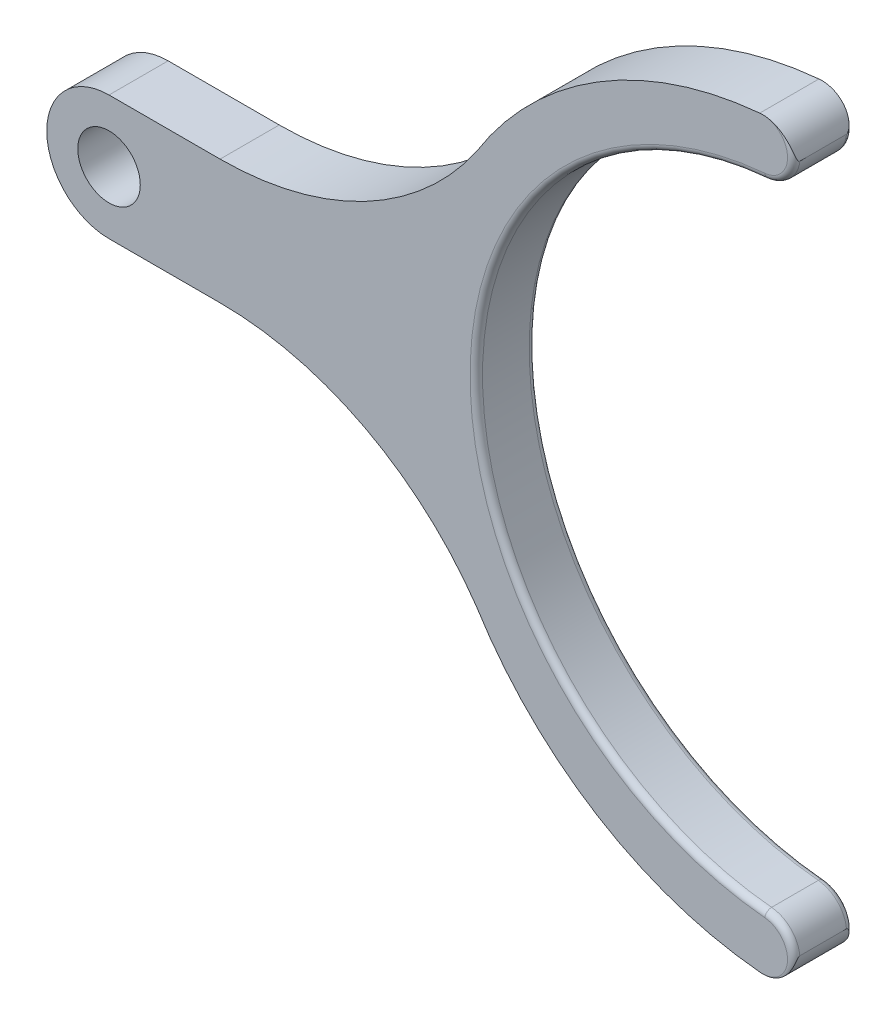
SolidWorks part; units mm, degrees
ref_plane "Front Plane" through (0, 0, 0) normal (0, 0, 1) x (1, 0, 0)
ref_plane "Top Plane" through (0, 0, 0) normal (0, 1, 0) x (1, 0, 0)
ref_plane "Right Plane" through (0, 0, 0) normal (1, 0, 0) x (0, 0, -1)
sketch "Sketch1" plane through (0, 0, 0) normal (0, 0, 1) x (1, 0, 0)
  line L0 (-319.8772, 0) -> (15673.9835, 0) construction
  line L1 (0, -319.8772) -> (0, 15673.9835) construction
  line L2 (51, -60) -> (51, -51)
  line L7 (-41.1562, 10) -> (-59, 10)
  line L9 (-41.1562, -10) -> (-59, -10)
  line L11 (51, 51) -> (51, 60)
  arc A0 (51, 51) -> (51, -51) centre (51, 0) ccw
  arc A1 (0, -31.607) -> (51, -60) centre (51, 0) ccw
  arc A2 (-41.1562, 10) -> (0, 31.607) centre (-41.1562, 60) ccw
  arc A3 (-41.1562, -10) -> (0, -31.607) centre (-41.1562, -60) cw
  arc A4 (-59, 10) -> (-59, -10) centre (-59, 0) ccw
  arc A5 (51, 60) -> (0, 31.607) centre (51, 0) ccw
  circle A6 centre (-59, 0) radius 5.02
  point P12 (-40, 0)
  point P22 (51, 0)
  dimension "D1" = 102
  dimension "D2" = 120
  dimension "D3" = 100
  dimension "D4" = 60
  dimension "D5" = 10
  dimension "D7" = 10.04
  dimension "D6" = 110
extrude "Boss-Extrude1" add sketch "Sketch1" along normal mid plane 9.5
fillet "Fillet2" radius 5 4 edges at (51, -60, 0) (51, -51, 0) (51, 60, 0) (51, 51, 0)
fillet "Fillet3" radius 1 6 edges at (49.5157, -52.2211, -4.75) (49.5157, 52.2211, -4.75) (49.5157, -52.2211, 4.75) (49.5157, 52.2211, 4.75) (0, 0, -4.75) (0, 0, 4.75)
